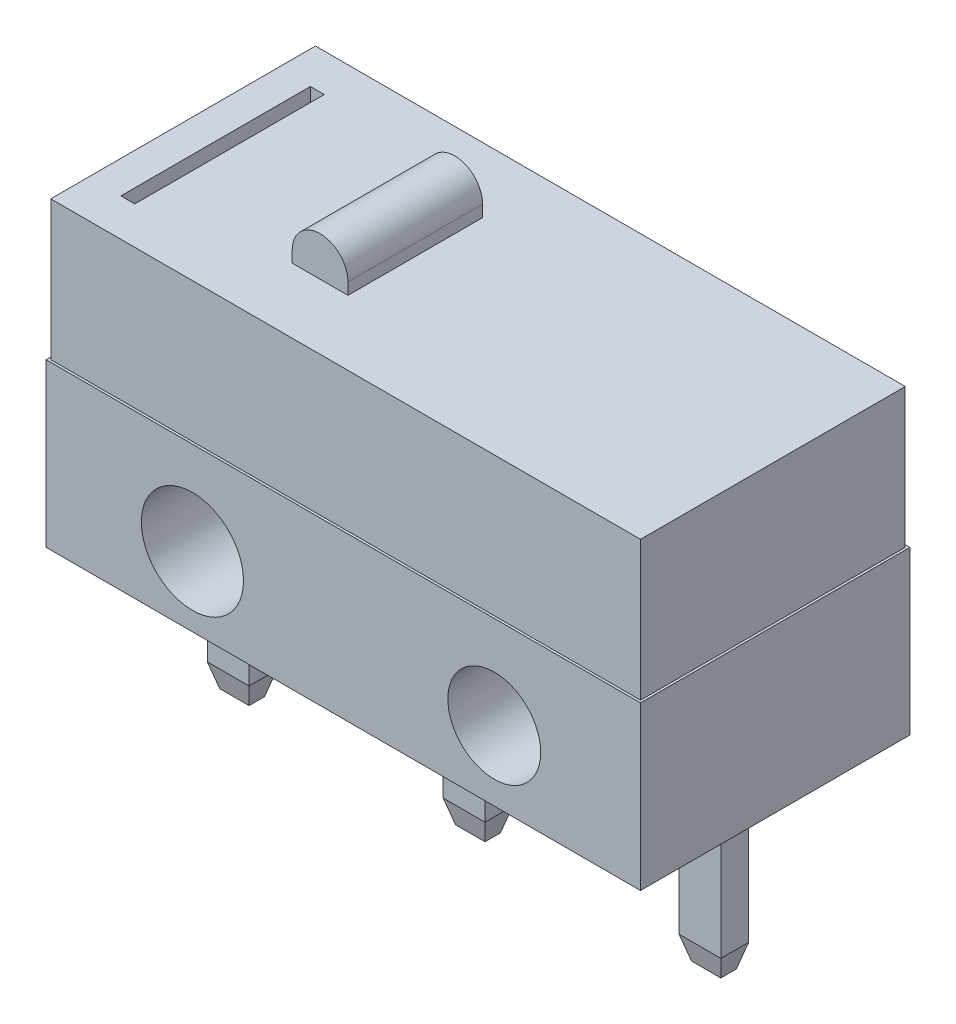
SolidWorks part; units mm, degrees
ref_plane "Front Plane" through (0, 0, 0) normal (0, 0, 1) x (1, 0, 0)
ref_plane "Top Plane" through (0, 0, 0) normal (0, 1, 0) x (1, 0, 0)
ref_plane "Right Plane" through (0, 0, 0) normal (1, 0, 0) x (0, 0, -1)
sketch "Sketch1" plane through (0, 0, 0) normal (0, 1, 0) x (1, 0, 0)
  line L1 (-6.4, -2.9) -> (6.4, -2.9)
  line L2 (-6.4, -2.9) -> (-6.4, 2.9)
  line L3 (-6.4, 2.9) -> (6.4, 2.9)
  line L4 (6.4, -2.9) -> (6.4, 2.9)
  line L5 (-6.4, -2.9) -> (6.4, 2.9) construction
  line L6 (-6.4, 2.9) -> (6.4, -2.9) construction
  point P0 (0, 0)
  dimension "D1" = 5.8
  dimension "D2" = 12.8
extrude "Boss-Extrude1" add sketch "Sketch1" along normal blind 3.5
sketch "Sketch2" plane through (0, 0, 0) normal (0, -1, 0) x (1, 0, 0)
  line L0 (-6.4, 0) -> (6.4, 0) construction
  line L1 (-6.4, -2.9) -> (-6.4, 2.9) construction
  line L2 (6.4, 2.9) -> (6.4, -2.9) construction
  line L3 (0, 2.9) -> (0, -2.9) construction
  line L4 (-6.4, 2.9) -> (6.4, 2.9) construction
  line L5 (6.4, -2.9) -> (-6.4, -2.9) construction
  line L6 (5.53, -0.3) -> (4.63, 0.3) construction
  line L7 (-0.45, -0.3) -> (0.45, -0.3)
  line L8 (-0.45, -0.3) -> (-0.45, 0.3)
  line L9 (-0.45, 0.3) -> (0.45, 0.3)
  line L10 (0.45, -0.3) -> (0.45, 0.3)
  line L11 (-0.45, -0.3) -> (0.45, 0.3) construction
  line L12 (-0.45, 0.3) -> (0.45, -0.3) construction
  line L13 (-5.53, -0.3) -> (-4.63, -0.3)
  line L14 (-5.53, -0.3) -> (-5.53, 0.3)
  line L15 (-5.53, 0.3) -> (-4.63, 0.3)
  line L16 (-4.63, -0.3) -> (-4.63, 0.3)
  line L17 (-5.53, -0.3) -> (-4.63, 0.3) construction
  line L18 (-5.53, 0.3) -> (-4.63, -0.3) construction
  line L19 (5.53, 0.3) -> (4.63, -0.3) construction
  line L20 (5.53, 0.3) -> (4.63, 0.3)
  line L21 (4.63, -0.3) -> (4.63, 0.3)
  line L22 (5.53, -0.3) -> (4.63, -0.3)
  line L23 (5.53, -0.3) -> (5.53, 0.3)
  point P12 (0, 0)
  point P18 (-5.08, 0)
  dimension "D1" = 0.6
  dimension "D2" = 0.9
  dimension "D3" = 5.08
extrude "Boss-Extrude3" add sketch "Sketch2" along normal blind 3.5
chamfer "Chamfer1" distance 0.5 angle 15 12 edges at (5.08, -3.5, -0.3) (4.63, -3.5, 0) (5.08, -3.5, 0.3) (5.53, -3.5, 0) (0, -3.5, -0.3) (-0.45, -3.5, 0) (0, -3.5, 0.3) (0.45, -3.5, 0) (-5.08, -3.5, -0.3) (-5.53, -3.5, 0) (-5.08, -3.5, 0.3) (-4.63, -3.5, 0) first distance on face at (5.08, -1.75, -0.3) first distance on face at (4.63, -1.75, 0) first distance on face at (5.08, -1.75, 0.3) first distance on face at (5.53, -1.75, 0) first distance on face at (0, -1.75, -0.3) first distance on face at (-0.45, -1.75, 0) first distance on face at (0, -1.75, 0.3) first distance on face at (0.45, -1.75, 0) first distance on face at (-5.08, -1.75, -0.3) first distance on face at (-5.53, -1.75, 0) first distance on face at (-5.08, -1.75, 0.3) first distance on face at (-4.63, -1.75, 0)
sketch "Sketch3" plane through (0, 0, 2.9) normal (0, 0, 1) x (1, 0, 0)
  line L0 (0, 3.5) -> (0, 0) construction
  line L1 (-6.4, 3.5) -> (6.4, 3.5) construction
  line L2 (-6.4, 1.5) -> (6.4, 1.5) construction
  line L3 (-6.4, 3.5) -> (-6.4, 0) construction
  line L4 (6.4, 3.5) -> (6.4, 0) construction
  circle A0 centre (-3.25, 1.5) radius 1.1
  circle A1 centre (3.25, 1.5) radius 1
  dimension "D2" = 2.2
  dimension "D3" = 2
  dimension "D1" = 1.5
  dimension "D4" = 3.15
  dimension "D5" = 3.15
extrude "Cut-Extrude1" cut sketch "Sketch3" against normal up to surface (5.8 mm away) up to face at (0, 1.75, -2.9)
sketch "Sketch4" plane through (0, 3.5, 0) normal (0, 1, 0) x (1, 0, 0)
  line L1 (6.35, -2.85) -> (-6.35, -2.85)
  line L2 (6.35, -2.85) -> (6.35, 2.85)
  line L3 (6.35, 2.85) -> (-6.35, 2.85)
  line L4 (-6.35, -2.85) -> (-6.35, 2.85)
  line L5 (6.35, -2.85) -> (-6.35, 2.85) construction
  line L6 (6.35, 2.85) -> (-6.35, -2.85) construction
  point P0 (0, 0)
  dimension "D1" = 5.7
  dimension "D2" = 12.7
extrude "Boss-Extrude4" add sketch "Sketch4" along normal blind 3
sketch "Sketch5" plane through (0, 0, 0) normal (0, 0, 1) x (1, 0, 0)
  line L0 (-1.95, 6.5) -> (-1.95, 7.35) construction
  line L1 (-6.35, 6.5) -> (6.35, 6.5) construction
  line L2 (-2.55, 6.5) -> (-2.55, 6.75)
  line L3 (-1.35, 6.5) -> (-1.35, 6.75)
  line L4 (-2.55, 6.5) -> (-1.35, 6.5)
  circle A1 centre (3.25, 1.5) radius 1 construction
  circle A2 centre (3.25, 1.5) radius 1 construction
  arc A3 (-2.55, 6.75) -> (-1.35, 6.75) centre (-1.95, 6.75) cw
  dimension "D1" = 5.2
  dimension "D2" = 1.2
  dimension "D3" = 0.85
extrude "Boss-Extrude5" add sketch "Sketch5" along normal blind 1.45 and the other way blind 1.45
sketch "Sketch6" plane through (0, 6.5, 0) normal (0, 1, 0) x (1, 0, 0)
  line L0 (-6.35, 0) -> (6.35, 0) construction
  line L3 (-6.35, 2.85) -> (-6.35, -2.85) construction
  line L4 (6.35, -2.85) -> (6.35, 2.85) construction
  line L6 (-5.35, -2.04) -> (-5.65, -2.04)
  line L7 (-5.35, -2.04) -> (-5.35, 2.04)
  line L8 (-5.35, 2.04) -> (-5.65, 2.04)
  line L9 (-5.65, -2.04) -> (-5.65, 2.04)
  line L10 (-5.35, -2.04) -> (-5.65, 2.04) construction
  line L11 (-5.35, 2.04) -> (-5.65, -2.04) construction
  point P6 (-5.5, 0)
  dimension "D1" = 0.7
  dimension "D2" = 4.08
  dimension "D3" = 0.3
extrude "Cut-Extrude2" cut sketch "Sketch6" against normal blind 0.4
